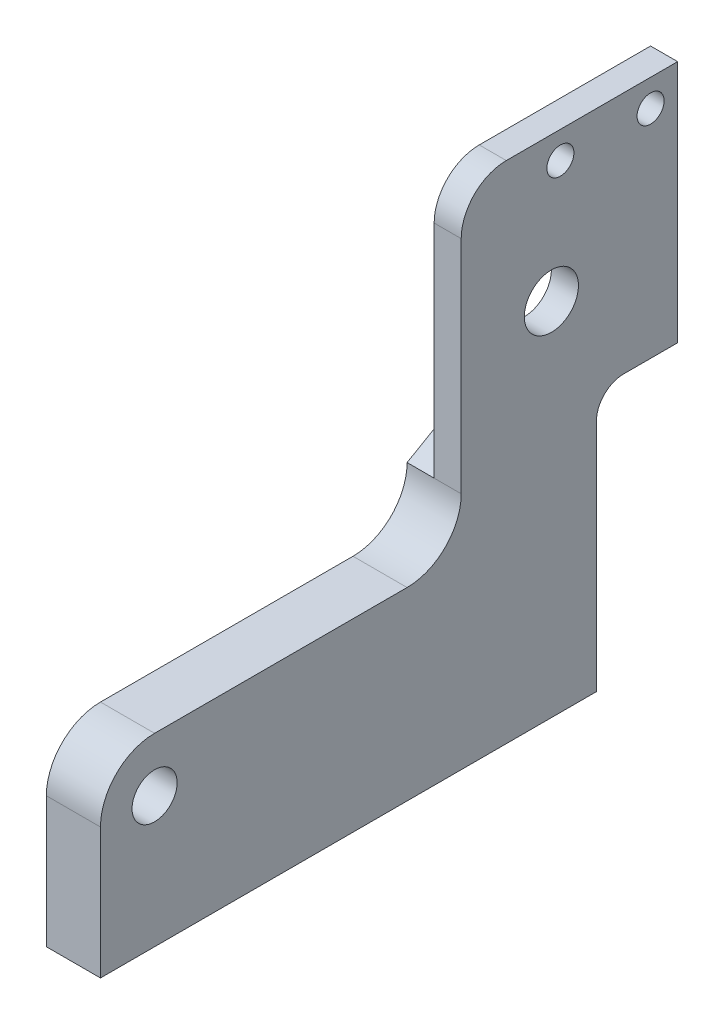
SolidWorks part; units mm, degrees
material "1060 Alloy"
ref_plane "Front Plane" through (0, 0, 0) normal (0, 0, 1) x (1, 0, 0)
ref_plane "Top Plane" through (0, 0, 0) normal (0, 1, 0) x (1, 0, 0)
ref_plane "Right Plane" through (0, 0, 0) normal (1, 0, 0) x (0, 0, -1)
sketch "Sketch1" plane through (0, 0, 0) normal (1, 0, 0) x (0, 0, -1)
  line L1 (0, 0) -> (64, 0)
  line L2 (0, 0) -> (0, 56)
  line L3 (0, 56) -> (64, 56)
  line L4 (64, 0) -> (64, 56)
  circle A0 centre (6, 14.5) radius 2.5
  circle A1 centre (50, 40) radius 3
  dimension "D1" = 6
  dimension "D2" = 5
  dimension "D3" = 14.5
  dimension "D4" = 6
  dimension "D5" = 40
  dimension "D6" = 50
  dimension "D7" = 64
  dimension "D8" = 56
extrude "Boss-Extrude1" add sketch "Sketch1" along normal blind 6
sketch "Sketch2" plane through (6, 0, 0) normal (1, 0, 0) x (0, 0, -1)
  line L0 (0, 56) -> (0, 0) construction
  line L2 (6, 20.5) -> (34, 20.5)
  line L4 (0, 14.5) -> (0, 57)
  line L5 (0, 57) -> (40, 57)
  line L6 (40, 57) -> (40, 26.5)
  line L7 (64, 56) -> (0, 56) construction
  arc A0 (0, 14.5) -> (6, 20.5) centre (6, 14.5) cw
  circle A1 centre (50, 40) radius 5 construction
  circle A2 centre (6, 14.5) radius 2.5 construction
  arc A4 (34, 20.5) -> (40, 26.5) centre (34, 26.5) ccw
  dimension "D2" = 10
  dimension "D1" = 1
  dimension "D3" = 40
extrude "Cut-Extrude1" cut sketch "Sketch2" against normal up to next
sketch "Sketch3" plane through (6, 0, 0) normal (1, 0, 0) x (0, 0, -1)
  line L0 (0, 14.5) -> (0, 0) construction
  line L57 (64, 0) -> (55, 0)
  line L58 (64, 0) -> (64, 29)
  line L59 (64, 29) -> (55, 29)
  line L60 (55, 0) -> (55, 29)
  dimension "D1" = 29
  dimension "D2" = 55
extrude "Cut-Extrude2" cut sketch "Sketch3" against normal up to next
fillet "Fillet1" radius 5 1 edges at (3, 56, -40)
fillet "Fillet2" radius 3 1 edges at (3, 29, -55)
hole_wizard "Tap Drill for M3 Tap1" positions "Sketch5" profile "Sketch4" hole size "M3" standard "ISO"
sketch "Sketch5" plane through (0, 0, 0) normal (0, -1, 0) x (-1, 0, 0)
  line L1 (-6, 0) -> (0, 0) construction
  line L2 (-6, 0) -> (-6, 55) construction
  point P0 (-3, 48)
  point P2 (-3, 12)
  dimension "D1" = 3
  dimension "D2" = 12
  dimension "D3" = 36
sketch "Sketch4" plane through (3, 0, -48) normal (1, 0, 0) x (0, 0, -1)
  line L0 (0, 0) -> (0, 10.7511)
  line L1 (0, 10.7511) -> (1.25, 10)
  line L2 (1.25, 10) -> (1.25, 0)
  line L5 (1.25, 0) -> (0, 0)
  line L10 (0, 10.7511) -> (-1.25, 10) construction
  line L11 (0, -6.35) -> (0, 107.95) construction
  dimension "Hole Dia." = 2.5
  dimension "Hole Depth" = 10
  dimension "Drill Angle" = 118
sketch "Sketch9" plane through (0, 0, 0) normal (-1, 0, 0) x (0, 0, 1)
  line L0 (-64, 56) -> (-64, 33.4282)
  line L1 (-64, 56) -> (-45, 56) construction
  line L3 (-64, 29) -> (-64, 56) construction
  line L4 (-64, 56) -> (-40, 56)
  line L5 (-40, 56) -> (-40, 26.5)
  line L6 (-52, 33.4282) -> (-64, 33.4282)
  line L11 (-40, 26.5) -> (-40, 51) construction
  line L12 (-40, 26.5) -> (-52, 33.4282)
  dimension "D1" = 12
  dimension "D5" = 60
extrude "Cut-Extrude3" cut sketch "Sketch9" against normal blind 3
sketch "Sketch10" plane through (3, 0, 0) normal (-1, 0, 0) x (0, 0, 1)
  line L0 (-45, 56) -> (-64, 56) construction
  line L1 (-64, 56) -> (-64, 33.4282) construction
  circle A0 centre (-61, 53) radius 1.5
  circle A1 centre (-51, 53) radius 1.5
  dimension "D1" = 3
  dimension "D2" = 3
  dimension "D3" = 3
  dimension "D4" = 10
extrude "Cut-Extrude4" cut sketch "Sketch10" against normal up to next
